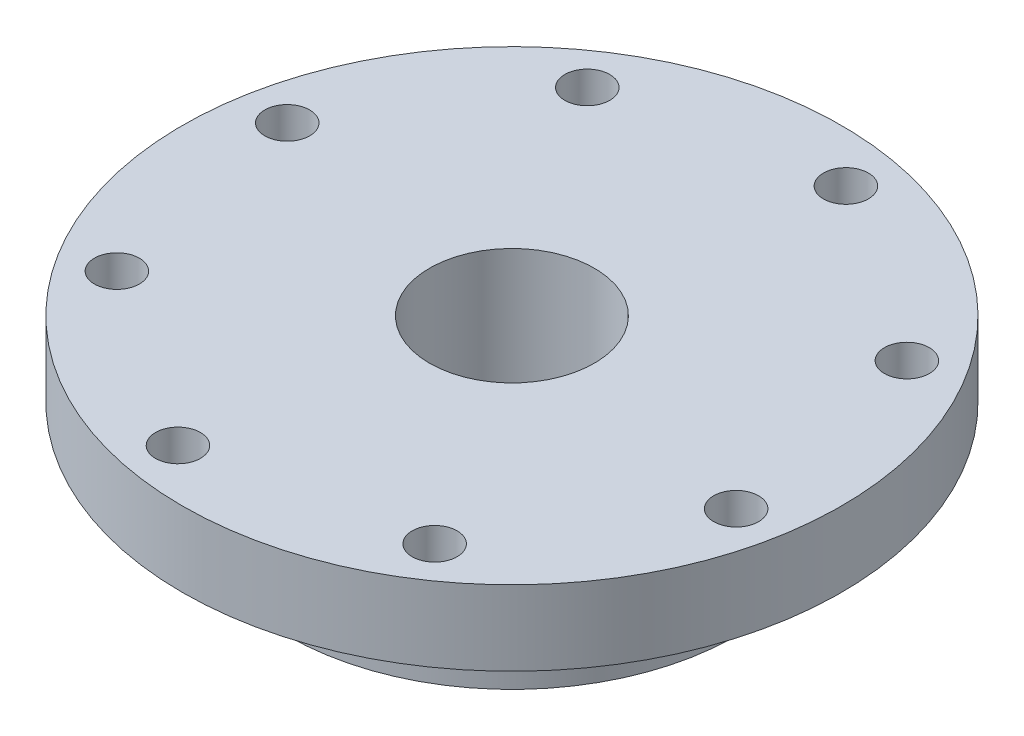
SolidWorks part; units mm, degrees
note: '?' marks a value the reader was unsure of.
ref_plane "Plan de face" through (0, 0, 0) normal (0, 0, 1) x (1, 0, 0)
ref_plane "Plan de dessus" through (0, 0, 0) normal (0, 1, 0) x (1, 0, 0)
ref_plane "Plan de droite" through (0, 0, 0) normal (1, 0, 0) x (0, 0, -1)
sketch "Esquisse1" plane through (0, 0, 0) normal (0, 0, 1) x (1, 0, 0)
  line L0 (0, 41.4701) -> (0, -61.8282) construction
  line L1 (-5.5, 0) -> (-22, 0)
  line L2 (-15, -11) -> (-15, -5)
  line L3 (-15, -11) -> (-11, -11)
  line L4 (-11, -11) -> (-11, -8.5)
  line L5 (-11, -8.5) -> (-5.5, -8.5)
  line L6 (-5.5, -8.5) -> (-5.5, 0)
  line L7 (-15, -5) -> (-22, -5)
  line L8 (-22, -5) -> (-22, 0)
  dimension "D1" = 5.5
  dimension "D2" = 15
  dimension "D3" = 11
  dimension "D4" = 8.5
  dimension "D5" = 11
  dimension "D6" = 5
  dimension "D7" = 22
revolve "Révolution1" add sketch "Esquisse1" angle 360 about L0
cosmetic thread "Représentation de filetage1" parameters "D1"=6, "D2"=28
sketch "Esquisse3" plane through (0, 0, 0) normal (0, 1, 0) x (1, 0, 0)
  line L0 (0, 0) -> (-10.2281, 15.2018) construction
  line L1 (0, 0) -> (16.1031, 10.8345) construction
  line L2 (16.1031, 10.8345) -> (0, 0) construction
  line L3 (0, 0) -> (10.0923, -15) construction
  line L4 (10.0923, -15) -> (0, 0) construction
  line L5 (0, 0) -> (-15.57, -10.4758) construction
  line L6 (3.0962, 15.8306) -> (-3.4114, -17.4419) construction
  line L7 (-18.825, 3.6819) -> (20.8567, -4.0793) construction
  circle A0 centre (0, 0) radius 19
  circle A1 centre (0, 0) radius 13.4143
  point P12 (-7.4883, 11.1297)
  point P13 (2.5749, 13.1649)
  point P14 (11.0511, 7.6038)
  point P15 (13.1649, -2.5749)
  point P16 (7.62, -11.0399)
  point P17 (-2.5749, -13.1649)
  point P18 (-11.2892, -7.2456)
  point P19 (-13.1649, 2.5749)
  dimension "D4" = 38
  dimension "D1" = 90
  dimension "D2" = 45
  dimension "D3" = 45
hole_wizard "Diamètre du perçage Ø3.0 (3)1" positions "Esquisse3D1" profile "Esquisse4" hole size "Ø3.0" standard "Ansi Métrique" end condition through all
sketch3d "Esquisse3D1"
  line L0 (3.0962, 0, -15.8306) -> (-3.4114, 0, 17.4419) construction
  line L1 (-18.825, 0, -3.6819) -> (20.8567, 0, 4.0793) construction
  line L2 (0, 0, 0) -> (-15.57, 0, 10.4758) construction
  line L3 (0, 0, 0) -> (10.0923, 0, 15) construction
  circle A0 centre (0, 0, 0) radius 19 construction
  point P0 (3.647, 0, -18.6467)
  point P4 (0, 19, 0)
  point P7 (15.7765, 0, -10.5878)
  point P9 (18.6413, 0, 3.6743)
  point P11 (-10.6824, 0, -15.7126)
  point P13 (-18.6467, 0, -3.647)
  point P17 (-15.764, 0, 10.6064)
  point P21 (-3.647, 0, 18.6467)
  point P23 (10.6064, 0, 15.764)
sketch "Esquisse4" plane through (3.647, 0, -18.6467) normal (1, 0, 0) x (0, 0, 1)
  line L0 (0, 0) -> (0, 11)
  line L1 (0, 11) -> (1.5, 11)
  line L2 (1.5, 11) -> (1.5, 0)
  line L5 (1.5, 0) -> (0, 0)
  line L11 (0, -6.35) -> (0, 107.95) construction
  dimension "Diamètre du perçage jusqu'au prochain" = 3
  dimension "Profondeur du perçage jusqu'au prochain" = 11
hole_wizard "Diamètre du perçage Ø4.0 (4)1" [suppressed] positions "Esquisse9" profile "Esquisse8" hole size "Ø4.0" standard "Ansi Métrique"
sketch "Esquisse9" plane through (0, 0, 0) normal (0, 1, 0) x (-1, 0, 0)
  line L0 (0, 0) -> (0, -20.3542) construction
  point P0 (0, -9)
  dimension "D1" = 9
sketch "Esquisse8" plane through (0, 0, -9) normal (1, 0, 0) x (0, 0, 1)
  line L0 (0, 0) -> (0, 6.2017)
  line L1 (0, 6.2017) -> (2, 5)
  line L2 (2, 5) -> (2, 0)
  line L5 (2, 0) -> (0, 0)
  line L10 (0, 6.2017) -> (-2, 5) construction
  line L11 (0, -6.35) -> (0, 107.95) construction
  dimension "Diamètre du perçage" = 4
  dimension "Profondeur du perçage" = 5
  dimension "Angle de pointe" = 118
ref_axis "Axe1" through (0, -8.5, 0) along (0, 1, 0)?
pattern_circular "Répétition circulaire1" [suppressed] count 8 over 360 about axis through (0, -8.5, 0) along (0, 1, 0)
